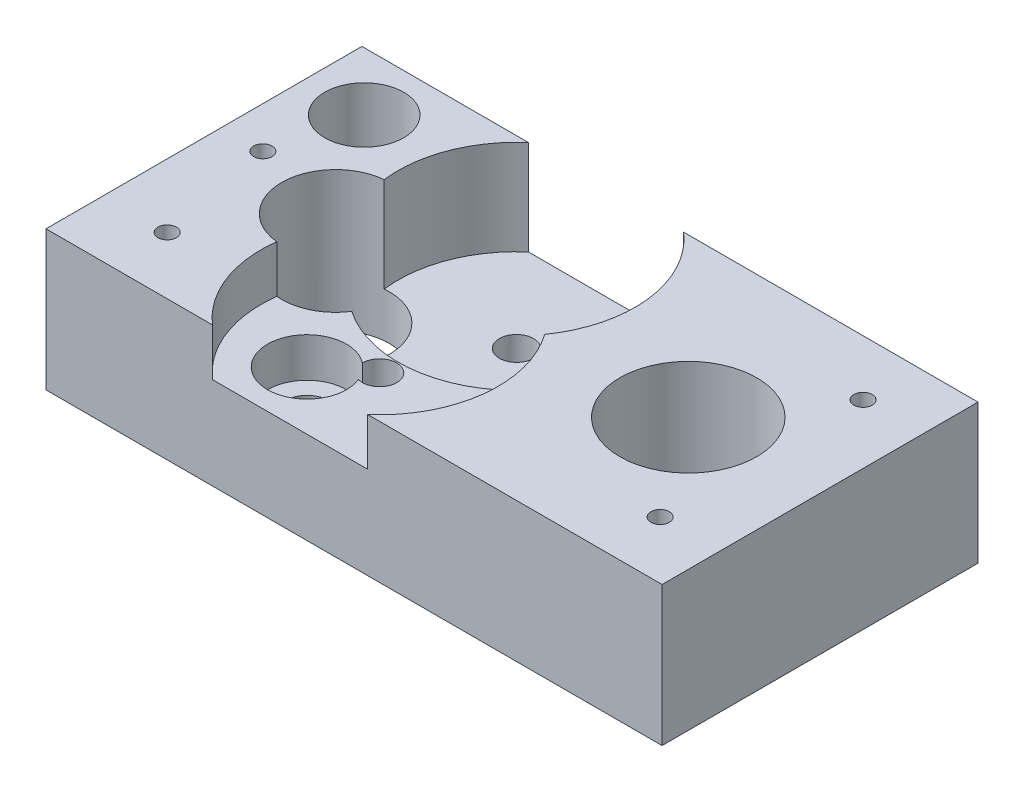
SolidWorks part; units mm, degrees
note: The reader was unsure of these and kept them because the rebuilt part matched: shared geometry of "草图3<16>", "草图5<10>".
ref_plane "前视基准面" through (0, 0, 0) normal (0, 0, 1) x (1, 0, 0)
ref_plane "上视基准面" through (0, 0, 0) normal (0, 1, 0) x (1, 0, 0)
ref_plane "右视基准面" through (0, 0, 0) normal (1, 0, 0) x (0, 0, -1)
other "Configuration Table"
sketch "草图1" plane through (0, 0, 0) normal (0, 1, 0) x (1, 0, 0)
  line L1 (0, 0) -> (23.4, 0)
  line L2 (0, 0) -> (0, -12)
  line L3 (0, -12) -> (23.4, -12)
  line L4 (23.4, 0) -> (23.4, -12)
  circle A0 centre (5, -6) radius 2.05
  circle A1 centre (9.2708, -8.6) radius 0.65
  circle A4 centre (18.3957, -6) radius 2.6
  circle A5 centre (9.2708, -3.4) radius 0.65
  point P9 (0, 0)
  point P12 (0, 0)
  point P13 (0, 0)
  point P14 (0, 0)
  dimension "D2" = 4.1
  dimension "D3" = 1.3
  dimension "D6" = 5.2
  dimension "D4" = 23.4
  dimension "D9" = 5
  dimension "D10" = 6
  dimension "D11" = 12
extrude "凸台-拉伸1" add sketch "草图1" along normal blind 1.7
sketch "草图3" plane through (0, 1.7, 0) normal (0, 1, 0) x (1, 0, 0)
  line L1 (0, 0) -> (23.4, 0)
  line L2 (0, 0) -> (0, -12)
  line L3 (0, -12) -> (23.4, -12)
  line L4 (23.4, 0) -> (23.4, -12)
  circle A0 centre (5, -6) radius 2.05
  circle A1 centre (5, -6) radius 2.05 construction
  circle A2 centre (9.2708, -8.6) radius 0.65
  circle A3 centre (9.2708, -8.6) radius 0.65 construction
  circle A4 centre (9.2708, -3.4) radius 4.5
  circle A6 centre (9.2708, -8.6) radius 4.5
  circle A10 centre (9.2708, -3.4) radius 0.65 construction
  point P5 (0, 0)
  circle M4 centre (18.3957, -6) radius 2.6
  line M5 (0, 0) -> (0, -12)
  line M6 (0, -12) -> (23.4, -12)
  line M7 (23.4, -12) -> (23.4, 0)
  line M8 (23.4, 0) -> (0, 0)
  circle M9 centre (5, -6) radius 2.05
  dimension "D1" = 9
sketch "草图5" plane through (0, 0, 0) normal (0, 1, 0) x (1, 0, 0)
  circle A0 centre (2.3, -2.2142) radius 0.8
  circle A1 centre (7.7, -9.7858) radius 0.8
  circle A4 centre (2.3, -2.2142) radius 1.5
  circle A5 centre (7.7, -9.7858) radius 1.5
  dimension "D1" = 1.6
  dimension "D2" = 3
extrude "凸台-拉伸3" add sketch "草图3" along normal blind 1.8
extrude "凸台-拉伸4" add sketch "草图3<16>" along normal blind 1.8 from surface at 1.8 contours A6 A4 M9 M8 M5 M6 | A6 A4 M6 M7 M8 M4 starting at face at (9.6525, 3.5, 4.876)
sketch "草图3<16>" plane through (0, 1.7, 0) normal (0, 1, 0) x (1, 0, 0) same geometry as "草图3"
extrude "切除-拉伸1" cut sketch "草图5" against normal through all from surface at 5.3 contours A1 | A0 starting at face at (3.2351, 5.3, 6)
extrude "切除-拉伸3" cut sketch "草图5<10>" against normal offset from surface (3.3 mm away) 2 from surface at 5.3 contours A5 | A4 up to face at (7.7, 0, 10.5858) starting at face at (2.3, 5.3, 3.0142)
sketch "草图5<10>" plane through (0, 0, 0) normal (0, 1, 0) x (1, 0, 0) same geometry as "草图5"
sketch "草图7" plane through (0, 5.3, 0) normal (0, 1, 0) x (1, 0, 0)
  circle A0 centre (1.5689, -5.3325) radius 0.35
  circle A1 centre (2.4192, -9.8175) radius 0.35
  circle A2 centre (21.1432, -2.1089) radius 0.35
  circle A3 centre (21.1432, -9.8175) radius 0.35
  point P8 (1.5725, -4.4873)
  point P9 (2.0106, -6.0123)
  point P10 (1.4113, -10.548)
  point P11 (2.4192, -9.8175)
  point P12 (1.5689, -5.3325)
  point P13 (21.1432, -2.1089)
  point P14 (21.1432, -9.8175)
  point P15 (0, 0)
  dimension "D1" = 0.7
extrude "切除-拉伸4" cut sketch "草图7" against normal blind 2
